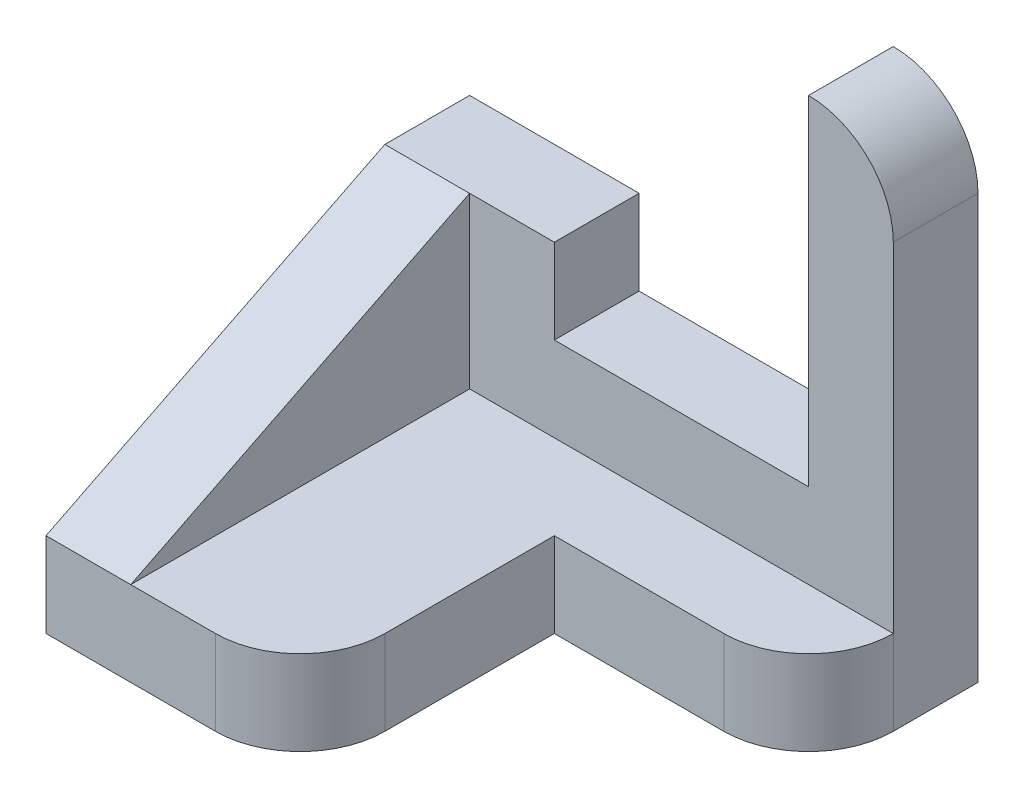
SolidWorks part; units mm, degrees
ref_plane "Front Plane" through (0, 0, 0) normal (0, 0, 1) x (1, 0, 0)
ref_plane "Top Plane" through (0, 0, 0) normal (0, 1, 0) x (1, 0, 0)
ref_plane "Right Plane" through (0, 0, 0) normal (1, 0, 0) x (0, 0, -1)
sketch "Sketch1" plane through (0, 0, 0) normal (0, 1, 0) x (1, 0, 0)
  line L0 (-52.8524, -30) -> (-52.8524, 20)
  line L1 (-52.8524, 20) -> (7.1476, 20)
  line L2 (7.1476, 20) -> (7.1476, 10)
  line L3 (-2.8524, 0) -> (-22.8524, 0)
  line L4 (-22.8524, 0) -> (-22.8524, -20)
  line L5 (-52.8524, -30) -> (-32.8524, -30)
  line L7 (-42.8524, 20) -> (-42.8524, -30)
  line L8 (-52.8524, 10) -> (7.1476, 10)
  line L10 (-32.8524, 20) -> (-32.8524, 10)
  line L12 (-2.8524, 20) -> (-2.8524, 10)
  arc A0 (7.1476, 10) -> (-2.8524, 0) centre (-2.8524, 10) cw
  arc A1 (-22.8524, -20) -> (-32.8524, -30) centre (-32.8524, -20) cw
  dimension "D1" = 10
  dimension "D2" = 10
  dimension "D9" = 52.8524
  dimension "D3" = 50
  dimension "D4" = 20
  dimension "D5" = 30
  dimension "D6" = 60
  dimension "D7" = 30
  dimension "D8" = 10
extrude "Boss-Extrude1" add sketch "Sketch1" along normal blind 20 contours L0 L8 L7 L1 region at (-47.8524, 0, -15)
extrude "Boss-Extrude2" add sketch "Sketch1<3>" along normal blind 20 contours L10 L1 L7 L8 region at (-37.8524, 0, -15)
sketch "Sketch1<3>" plane through (0, 0, 0) normal (0, 1, 0) x (1, 0, 0) same geometry as "Sketch1"
extrude "Boss-Extrude3" add sketch "Sketch1<4>" along normal blind 20 contours L8 L0 L5 L7 region at (-47.8524, 0, 10)
sketch "Sketch1<4>" plane through (0, 0, 0) normal (0, 1, 0) x (1, 0, 0) same geometry as "Sketch1"
extrude "Boss-Extrude4" add sketch "Sketch1<5>" along normal blind 50 separate body contours L1 L12 L8 L2 region at (2.1476, 0, -15)
sketch "Sketch1<5>" plane through (0, 0, 0) normal (0, 1, 0) x (1, 0, 0) same geometry as "Sketch1"
extrude "Boss-Extrude5" add sketch "Sketch1<6>" along normal blind 10 contours L12 L1 L10 L8 region at (-17.8524, 0, -15)
sketch "Sketch1<6>" plane through (0, 0, 0) normal (0, 1, 0) x (1, 0, 0) same geometry as "Sketch1"
chamfer "Chamfer1" distance 20 angle 63.43 1 edges at (-47.8524, 20, 30) first distance on face at (-47.8524, 10, 30)
fillet "Fillet1" radius 10 1 edges at (7.1476, 50, -15)
extrude "Boss-Extrude6" add sketch "Sketch1<7>" against normal blind 10 contours L8 L0 L5 L7 | A1 L4 L3 A0 L8 L7 L5 | L0 L8 L7 L1 | L10 L1 L7 L8 | L12 L1 L10 L8 | L1 L12 L8 L2 region at (-47.8524, 0, 10) region at (-47.8524, 0, -15) region at (-26.6817, 0, 5.6307) region at (-37.8524, 0, -15) region at (-17.8524, 0, -15) region at (2.1476, 0, -15)
sketch "Sketch1<7>" plane through (0, 0, 0) normal (0, 1, 0) x (1, 0, 0) same geometry as "Sketch1"
